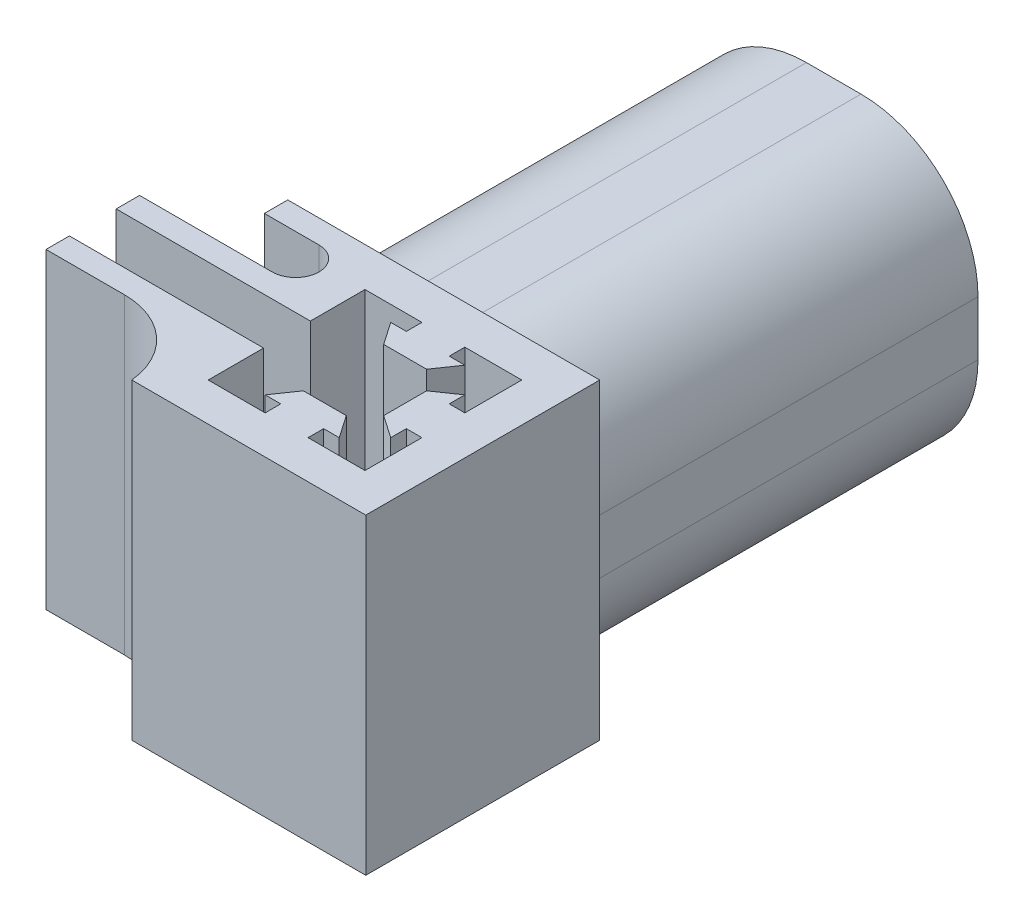
SolidWorks part; units mm, degrees
ref_plane "Front Plane" through (0, 0, 0) normal (0, 0, 1) x (1, 0, 0)
ref_plane "Top Plane" through (0, 0, 0) normal (0, 1, 0) x (1, 0, 0)
ref_plane "Right Plane" through (0, 0, 0) normal (1, 0, 0) x (0, 0, -1)
sketch "Sketch5" plane through (0, 0, 0) normal (0, 1, 0) x (1, 0, 0)
  line L1 (0, 0) -> (30, 0)
  line L2 (0, 0) -> (0, -30)
  line L3 (0, -30) -> (30, -30)
  line L4 (30, 0) -> (30, -30)
  dimension "D1" = 30
  dimension "D2" = 30
extrude "Boss-Extrude3" add sketch "Sketch5" along normal blind 40 contours L1 L4 L3 L2
sketch "Sketch6" plane through (0, 40, 0) normal (0, 1, 0) x (1, 0, 0)
  line L0 (0, 0) -> (0, -30) construction
  line L1 (4.9, -5) -> (25, -5)
  line L2 (4.9, -5) -> (4.9, -25.1)
  line L3 (4.9, -25.1) -> (25, -25.1)
  line L4 (25, -5) -> (25, -25.1)
  line L5 (0, -30) -> (30, -30) construction
  line L6 (12.2, -5) -> (12.2, -7)
  line L7 (12.2, -7) -> (10.2, -7)
  line L8 (17.7, -5) -> (17.7, -7)
  line L9 (17.7, -7) -> (19.7, -7)
  line L10 (4.9, -15.05) -> (25, -15.05) construction
  line L11 (10.2, -7) -> (12.2, -9.9)
  line L12 (19.7, -7) -> (17.7, -9.9)
  line L13 (12.2, -9.9) -> (17.7, -9.9)
  line L14 (19.7, -23.1) -> (17.7, -20.2)
  line L15 (17.7, -23.1) -> (19.7, -23.1)
  line L16 (17.7, -25.1) -> (17.7, -23.1)
  line L17 (12.2, -25.1) -> (12.2, -23.1)
  line L18 (12.2, -23.1) -> (10.2, -23.1)
  line L19 (10.2, -23.1) -> (12.2, -20.2)
  line L20 (12.2, -20.2) -> (17.7, -20.2)
  line L21 (25, -12.3) -> (23, -12.3)
  line L22 (23, -12.3) -> (23, -10.3)
  line L23 (23, -10.3) -> (20.1, -12.3)
  line L24 (20.1, -12.3) -> (20.1, -17.8)
  line L25 (23, -19.8) -> (20.1, -17.8)
  line L26 (23, -17.8) -> (23, -19.8)
  line L27 (25, -17.8) -> (23, -17.8)
  point P32 (20.1, -15.05)
  dimension "D1" = 20.1
  dimension "D2" = 20.1
  dimension "D3" = 4.9
  dimension "D4" = 4.9
  dimension "D5" = 2
  dimension "D6" = 7.3
  dimension "D7" = 2
  dimension "D8" = 7.3
  dimension "D9" = 2
  dimension "D10" = 2
  dimension "D11" = 2
  dimension "D12" = 7.3
  dimension "D13" = 2
  dimension "D14" = 2.9
  dimension "D15" = 2
  dimension "D16" = 2
  dimension "D17" = 2.9
  dimension "D18" = 2
extrude "Cut-Extrude1" cut sketch "Sketch6" against normal blind 50 contours L2 L10 L24 L23 L22 L21 L4 L1 L8 L9 L12 L13 L11 L7 L6 | L10 L2 L3 L17 L18 L19 L20 L14 L15 L16 L4 L27 L26 L25 L24 region at (14.1458, 40, 10.2048) region at (14.1458, 40, 19.8952)
sketch "Sketch8" plane through (0, 40, 0) normal (0, 1, 0) x (1, 0, 0)
  line L0 (4.9, -5) -> (4.9, -25.1) construction
  line L1 (4.9, -12) -> (0, -12)
  line L2 (4.9, -12) -> (4.9, -18)
  line L3 (4.9, -18) -> (0, -18)
  line L4 (0, -12) -> (0, -18)
  line L5 (0, 0) -> (0, -30) construction
  line L6 (0, 0) -> (30, 0) construction
  dimension "D1" = 6
  dimension "D2" = 12
extrude "Cut-Extrude3" cut sketch "Sketch8" against normal blind 40 contours L4 L3 L2 L1
sketch "Sketch10" plane through (0, 0, 0) normal (-1, 0, 0) x (0, 0, 1)
  line L0 (0, 0) -> (12, 0) construction
  line L10 (0, 0) -> (12, 0) construction
  line L11 (0, 40) -> (3, 40)
  line L12 (0, 40) -> (0, 0)
  line L13 (0, 0) -> (3, 0)
  line L14 (3, 40) -> (3, 0)
  line L15 (9, 0) -> (12, 0)
  line L16 (9, 0) -> (9, 40)
  line L17 (9, 40) -> (12, 40)
  line L18 (12, 0) -> (12, 40)
  line L19 (0, 40) -> (12, 40) construction
  line L21 (18, 0) -> (21, 0)
  line L22 (18, 0) -> (18, 40)
  line L23 (18, 40) -> (21, 40)
  line L24 (21, 0) -> (21, 40)
  dimension "D1" = 3
  dimension "D2" = 3
  dimension "D3" = 3
  dimension "D4" = 6
  dimension "D5" = 6
extrude "Boss-Extrude4" add sketch "Sketch10" along normal blind 10
sketch "Sketch11" plane through (0, 0, 0) normal (0, 0, -1) x (-1, 0, 0)
  line L0 (10, 40) -> (10, 0) construction
  line L5 (-28.5, 38.5) -> (8.5, 38.5)
  line L6 (-28.5, 38.5) -> (-28.5, 1.5)
  line L7 (-28.5, 1.5) -> (8.5, 1.5)
  line L8 (8.5, 38.5) -> (8.5, 1.5)
  line L9 (10, 40) -> (-30, 40) construction
  line L10 (-30, 40) -> (-30, 0) construction
  dimension "D1" = 1.5
  dimension "D2" = 1.5
  dimension "D3" = 1.5
  dimension "D4" = 1.5
extrude "Boss-Extrude5" add sketch "Sketch11" along normal blind 50 contours L7 L8 L5 L6
sketch "Sketch14" plane through (0, 0, -50) normal (0, 0, -1) x (-1, 0, 0)
  line L0 (-10, 38.5) -> (-10.2, 0) construction
  line L1 (-28.5, 38.5) -> (8.5, 38.5) construction
  circle A0 centre (-10.1, 19.25) radius 13.5 construction
  circle A1 centre (-10.1, 32.75) radius 1.5
  circle A2 centre (1.5913, 12.5) radius 1.5
  circle A3 centre (-21.7913, 12.5) radius 1.5
  point P15 (-10.1, 19.25)
  dimension "D1" = 27
  dimension "D2" = 3
  dimension "D3" = 3
  dimension "D4" = 20.25
  dimension "D5" = 11.6913
extrude "Cut-Extrude4" cut sketch "Sketch14" against normal blind 20
fillet "Fillet2" radius 15 4 edges at (-8.5, 1.5, -25) (-8.5, 38.5, -25) (28.5, 38.5, -25) (28.5, 1.5, -25)
fillet "Fillet3" 2 edges at (0, 20, 3) (0, 20, 9) type full round first side face at (-5, 20, 3) second side face at (-5, 20, 9) middle face at (0, 20, 6)
fillet "Fillet4" radius 10 1 edges at (0, 20, 21)
sketch "Sketch15" plane through (-10, 0, 0) normal (-1, 0, 0) x (0, 0, 1)
  line L0 (18, 0) -> (21, 0) construction
  line L1 (9, 40) -> (12, 40)
  line L2 (9, 40) -> (9, 0)
  line L3 (9, 0) -> (12, 0)
  line L4 (12, 40) -> (12, 0)
  line L5 (18, 40) -> (21, 40)
  line L6 (18, 40) -> (18, 0)
  line L7 (18, 0) -> (21, 0)
  line L8 (21, 40) -> (21, 0)
  line L9 (21, 0) -> (21, 40) construction
extrude "Boss-Extrude6" add sketch "Sketch15" along normal blind 10
